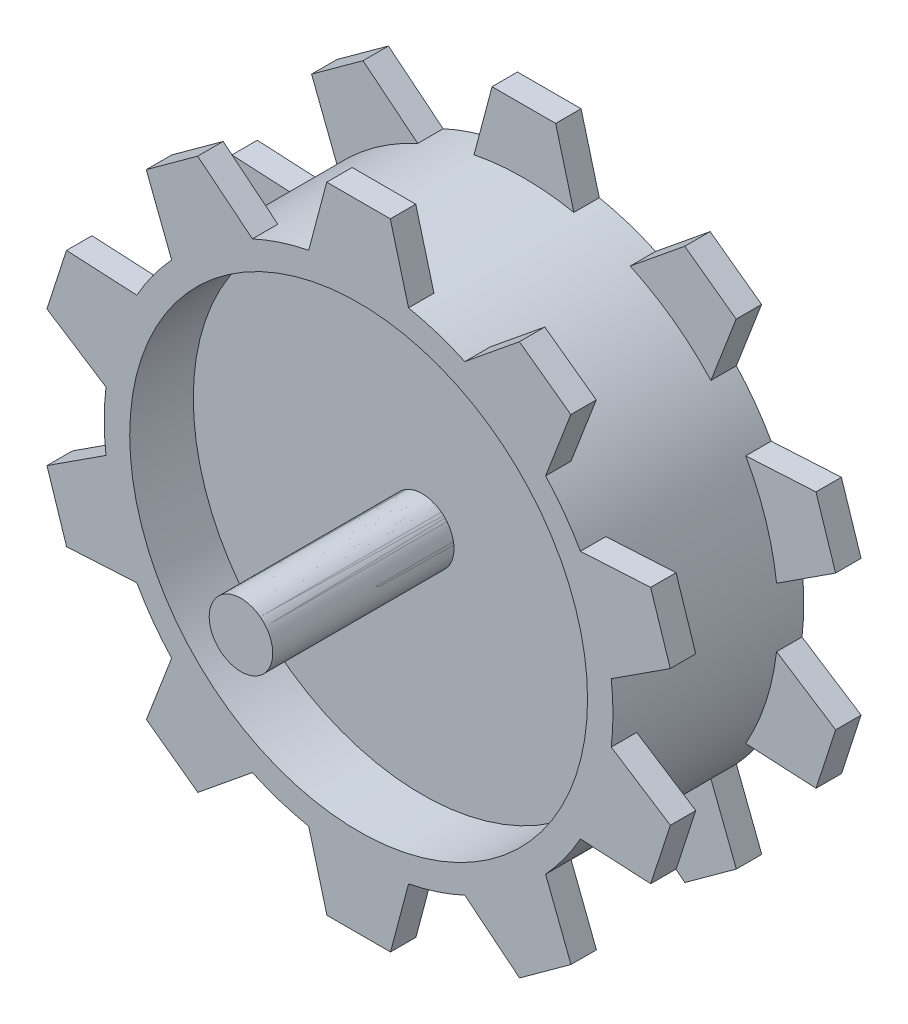
SolidWorks part; units mm, degrees
other "Markup1"
sketch "Sketch8" plane through (245.1125, 249.576, 242.5) normal (0.7937, 0.1741, 0.5829) x (0.593, -0.0075, -0.8052)
ref_plane "Front Plane" through (0, 0, 0) normal (0, 0, 1) x (1, 0, 0)
ref_plane "Top Plane" through (0, 0, 0) normal (0, 1, 0) x (1, 0, 0)
ref_plane "Right Plane" through (0, 0, 0) normal (1, 0, 0) x (0, 0, -1)
sketch "Sketch2" plane through (0, 0, 0) normal (0, 0, 1) x (1, 0, 0)
  circle A0 centre (0, 0) radius 200
  dimension "D1" = 400
extrude "Boss-Extrude1" add sketch "Sketch2" along normal blind 150
ref_plane "Plane1" through (0, 0, 75) normal (0, 0, 1) x (1, 0, 0)
sketch "Sketch3" plane through (0, 0, 150) normal (0, 0, 1) x (1, 0, 0)
  line L4 (-25.0848, 249.576) -> (24.9152, 249.576)
  line L7 (24.9152, 249.576) -> (39.2406, 196.1127)
  line L8 (-25.0848, 249.576) -> (-39.2406, 196.1127)
  circle A0 centre (0, 0) radius 200 construction
  arc A2 (39.2406, 196.1127) -> (-39.2406, 196.1127) centre (0, 0) ccw
  dimension "D2" = 105
  dimension "D3" = 50
extrude "Boss-Extrude2" add sketch "Sketch3" against normal blind 20
pattern_circular "CirPattern1" count 10 over 360 about axis through (0, 0, 150) along (0, 0, 1) of "Boss-Extrude2"
mirror "Mirror1" about plane through (0, 0, 75) normal (0, 0, 1) of "CirPattern1"
sketch "Sketch4" plane through (0, 0, 0) normal (0, 0, -1) x (-1, 0, 0)
  circle A0 centre (0, 0) radius 25
  dimension "D1" = 50
extrude "Cut-Extrude1" cut sketch "Sketch4" against normal through all
sketch "Sketch6" plane through (0, 0, 150) normal (0, 0, 1) x (1, 0, 0)
  circle A0 centre (0, 0) radius 180
  dimension "D1" = 360
extrude "Cut-Extrude2" cut sketch "Sketch6" against normal blind 50
mirror "Mirror2" about plane through (0, 0, 75) normal (0, 0, 1) of "Cut-Extrude2"
sketch "Sketch7" plane through (0, 0, 50) normal (0, 0, -1) x (-1, 0, 0)
  circle A0 centre (0, 0) radius 25
extrude "Boss-Extrude4" add sketch "Sketch7<2>" along normal blind 1 and the other way blind 192.5 separate body
sketch "Sketch7<2>" plane through (0, 0, 50) normal (0, 0, -1) x (-1, 0, 0) same geometry as "Sketch7"
extrude "Boss-Extrude3" add sketch "Sketch7" against normal blind 192.5 separate body
